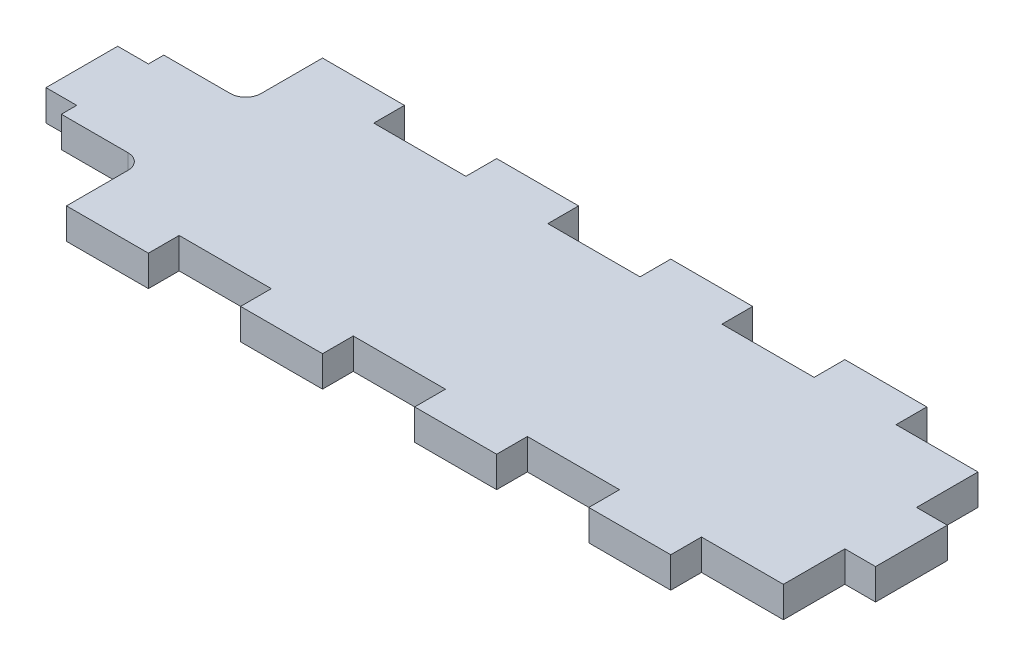
SolidWorks part; units mm, degrees
ref_plane "Front Plane" through (0, 0, 0) normal (0, 0, 1) x (1, 0, 0)
ref_plane "Top Plane" through (0, 0, 0) normal (0, 1, 0) x (1, 0, 0)
ref_plane "Right Plane" through (0, 0, 0) normal (1, 0, 0) x (0, 0, -1)
sketch "Sketch1" plane through (0, 0, 0) normal (0, 1, 0) x (1, 0, 0)
  line L0 (-81, 0) -> (-71, 0) construction
  line L1 (-81, 25) -> (81, 25)
  line L2 (-81, 25) -> (-81, -25)
  line L3 (-81, -25) -> (81, -25)
  line L4 (81, 25) -> (81, -25)
  line L5 (-81, 25) -> (81, -25) construction
  line L6 (-81, -25) -> (81, 25) construction
  line L7 (-81, 25) -> (-71, 25)
  line L8 (-81, 25) -> (-81, -25)
  line L9 (-81, -25) -> (-71, -25)
  line L10 (-71, 25) -> (-71, -25)
  line L12 (-81, -10) -> (-71, -10)
  line L13 (-81, -10) -> (-81, 10)
  line L14 (-81, 10) -> (-71, 10)
  line L15 (-71, -10) -> (-71, 10)
  line L16 (-81, -10) -> (-71, 10) construction
  line L17 (-81, 10) -> (-71, -10) construction
  point P0 (0, 0)
  point P10 (-76, 0)
  dimension "D3" = 10
  dimension "D4" = 20
  dimension "D2" = 50
  dimension "D1" = 162
sketch "Sketch2" plane through (0, 0, 0) normal (0, 0, 1) x (1, 0, 0)
  line L0 (0, 0) -> (0, 6) construction
  line L1 (-81, 0) -> (81, 0) construction
extrude "Boss-Extrude1" add sketch "Sketch1" along normal up to vertex (6 mm away) contours L2 L3 L4 L1 up to point (0, 6, 0)
sketch "Sketch3" plane through (0, 6, 0) normal (0, 1, 0) x (1, 0, 0)
  line L0 (-81, 25) -> (-81, -25) construction
  line L1 (-81, 10) -> (-59, 10) construction
  line L2 (-81, 10) -> (-81, -10) construction
  line L3 (-81, -10) -> (-59, -10) construction
  line L4 (-59, 10) -> (-59, -10) construction
  line L5 (-59, 19.2244) -> (-59, -19.2244) construction
  line L6 (0, 0) -> (-59, 0) construction
  line L7 (-81, 19) -> (-75, 19) construction
  line L8 (-81, -25) -> (-59, -25) construction
  line L9 (-81, -25) -> (-81, -19) construction
  line L10 (-81, -19) -> (-59, -19) construction
  line L11 (-59, -25) -> (-59, -19) construction
  line L12 (-81, 25) -> (-59, 25) construction
  line L13 (-81, 25) -> (-81, 19) construction
  line L14 (-81, 19) -> (-59, 19) construction
  line L15 (-59, 25) -> (-59, 19) construction
  line L16 (-75, 19) -> (-75, 10) construction
  line L18 (-75, 19) -> (-59, 19)
  line L19 (-75, 19) -> (-75, 10)
  line L20 (-75, 10) -> (-59, 10)
  line L21 (-59, 19) -> (-59, 10)
  line L22 (-59, -10) -> (-75, -10)
  line L23 (-59, -10) -> (-59, -19)
  line L24 (-59, -19) -> (-75, -19)
  line L25 (-75, -10) -> (-75, -19)
  point P26 (-75, -19.05)
  dimension "D1" = 20
  dimension "D2" = 6
  dimension "D3" = 22
extrude "Cut-Extrude1" cut sketch "Sketch3" against normal through all
sketch "Sketch4" plane through (0, 6, 0) normal (0, 1, 0) x (1, 0, 0)
  line L0 (-59, -19) -> (-59, -25)
  line L1 (-81, -25) -> (81, -25) construction
  line L2 (-59, 19) -> (-59, 25)
  line L3 (-81, 25) -> (81, 25) construction
  line L4 (-59, 19) -> (-75, 19)
  line L5 (-75, 19) -> (-75, 7)
  line L6 (-75, 7) -> (-81, 7)
  line L7 (-81, 7) -> (-81, -7)
  line L8 (81, 25) -> (-81, 25)
  line L9 (-81, 25) -> (-81, -25)
  line L10 (-81, -25) -> (81, -25)
  line L11 (81, -25) -> (81, 25)
  line L12 (81, 25) -> (-81, 25)
  line L13 (-81, 25) -> (-81, -25)
  line L14 (-81, -25) -> (81, -25)
  line L15 (81, -25) -> (81, 25)
  line L16 (-81, -7) -> (-75, -7)
  line L17 (-75, -7) -> (-75, -19)
  line L18 (-75, -19) -> (-59, -19)
  line L19 (-75, 10) -> (-59, 10) construction
  line M10 (-59, -19) -> (-75, -19)
  line M11 (-75, -19) -> (-75, -10)
  line M12 (-75, 19) -> (-59, 19)
  line M15 (-75, 10) -> (-75, 19)
  line M16 (81, 25) -> (-81, 25)
  line M17 (-81, 25) -> (-81, -25)
  line M18 (-81, -25) -> (81, -25)
  dimension "D2" = 3
  dimension "D1" = 0
extrude "Cut-Extrude2" cut sketch "Sketch4" against normal through all contours L6 L5 L2 M15 M12 M16 M17 | L17 L16 L0 M17 M18 M10 M11 region at (-59.2843, 6, 22) region at (-80.7157, 6, -16)
sketch "Sketch6" plane through (0, 6, 0) normal (0, 1, 0) x (1, 0, 0)
  line L0 (-59, -25) -> (81, -25) construction
  line L1 (-43, -19) -> (-59, -19) construction
  line L2 (-43, -19) -> (-43, -25)
  line L3 (-43, -25) -> (-59, -25)
  line L4 (-59, -19) -> (-59, -25)
  line L5 (-25, -19) -> (-9, -19) construction
  line L6 (-25, -19) -> (-25, -25)
  line L7 (-25, -25) -> (-9, -25)
  line L8 (-9, -19) -> (-9, -25)
  line L9 (-9, -19) -> (-9, -25) construction
  line L10 (75, -25) -> (-75, -25) construction
  line L11 (-43, -19) -> (-25, -19)
  line L12 (-43, -19) -> (-43, -25)
  line L13 (-43, -25) -> (-25, -25)
  line L14 (-25, -19) -> (-25, -25)
  line L15 (-9, -19) -> (0, -19)
  line L16 (-9, -19) -> (-9, -25)
  line L17 (-9, -25) -> (0, -25)
  line L18 (0, -19) -> (0, -25)
  point P18 (0, -23.6714)
  point P20 (0, 0)
  line M11 (-59, -25) -> (81, -25)
extrude "Cut-Extrude3" cut sketch "Sketch6" against normal through all contours L11 L2 L6 M11 | L18 L15 L8 M11 region at (-34, 6, 22) region at (-4.5, 6, 22)
mirror "Mirror1" about plane through (0, 0, 0) normal (0, 0, 1) of "Cut-Extrude3"
mirror "Mirror2" about plane through (0, 0, 0) normal (1, 0, 0) of "Mirror1"
sketch "Sketch7" plane through (0, 6, 0) normal (0, 1, 0) x (1, 0, 0)
  line L0 (81, 25) -> (81, -25) construction
  line L1 (59, -19) -> (81, -19)
  line L2 (59, -19) -> (59, -25)
  line L3 (59, -25) -> (81, -25)
  line L4 (81, -19) -> (81, -25)
  line L5 (81, -7) -> (75, -7)
  line L6 (81, -7) -> (81, -25)
  line L7 (81, -25) -> (75, -25)
  line L8 (75, -7) -> (75, -25)
  line L9 (-81, -7) -> (-75, -7) construction
  line M7 (43, -25) -> (81, -25)
  line M8 (81, -25) -> (81, 25)
extrude "Cut-Extrude4" cut sketch "Sketch7" against normal through all contours L8 L1 L2 M7 | L1 L8 L3 M8 | L5 L8 L1 M8 region at (67, 6, 22) region at (78, 6, 13) region at (78, 6, 22)
mirror "Mirror3" about plane through (0, 0, 0) normal (0, 0, 1) of "Cut-Extrude4"
fillet "Fillet1" radius 3 2 edges at (-59, 3, -10) (-59, 3, 10)
equation "\"glass_width\"= 150"
equation "\"glass_height\"= 100"
equation "\"glass_thickness\"= 4"
equation "\"brood_space\"= 42"
equation "\"t1\"= 6"
equation "\"t2\"= 6"
equation "\"box_depth\"= \"brood_space\" + \"glass_thickness\" + \"glass_thickness\" + \"t2\" + \"t2\""
equation "\"box_width\"= \"glass_width\" + \"t1\" + \"t1\""
equation "\"food_height\"= 70"
equation "\"box_height\"= \"glass_height\" + ( \"t1\" * 3 ) + \"food_height\""
equation "\"D1@Sketch2\"=\"t1\""
equation "\"entry_height\"= 24"
equation "\"entry_diameter\"= 8"
equation "\"food_top_clearance\"= 10"
equation "\"bar_width\"= 20"
equation "\"glassblocker_lower_height\"= 10"
equation "\"D2@Sketch1\"=\"brood_space\"+\"glass_thickness\"+\"glass_thickness\""
equation "\"D2@Sketch3\"=\"t1\""
equation "\"D1@Sketch1\"=\"box_width\""
